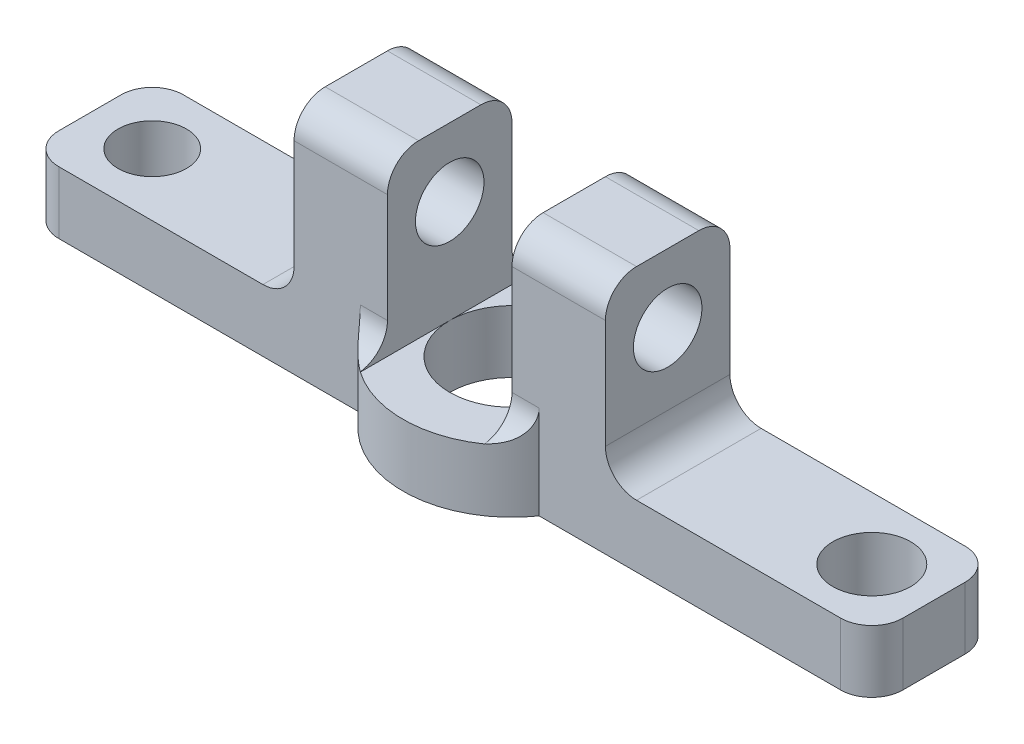
SolidWorks part; units mm, degrees
ref_plane "前视基准面" through (0, 0, 0) normal (0, 0, 1) x (1, 0, 0)
ref_plane "上视基准面" through (0, 0, 0) normal (0, 1, 0) x (1, 0, 0)
ref_plane "右视基准面" through (0, 0, 0) normal (1, 0, 0) x (0, 0, -1)
other "Configuration Table"
sketch "草图1" plane through (0, 0, 0) normal (0, 1, 0) x (1, 0, 0)
  line L0 (-9.561, 0) -> (15.394, 0) construction
  line L5 (15.394, -2) -> (6.0751, -2)
  line L9 (-7.716, 2) -> (1.6029, 2)
  line L11 (6.0751, 2) -> (15.394, 2) construction
  line L13 (15.394, -2) -> (6.0751, -2) construction
  line L18 (-7.716, 2) -> (-9.716, 2)
  line L19 (-9.716, 2) -> (-9.716, -2)
  line L20 (-9.716, -2) -> (-7.716, -2)
  line L21 (15.394, 2) -> (17.394, 2)
  line L22 (17.394, 2) -> (17.394, -2)
  line L23 (17.394, -2) -> (15.394, -2)
  line L24 (6.0751, 2) -> (15.394, 2)
  line L25 (1.6029, -2) -> (-7.716, -2)
  line L26 (1.6029, -2) -> (-7.716, -2) construction
  circle A2 centre (-7.716, 0) radius 1.1
  circle A3 centre (15.394, 0) radius 1.25
  circle A4 centre (3.839, 0) radius 2
  circle A6 centre (3.839, 0) radius 3.5
extrude "凸台-拉伸1" add sketch "草图1" along normal blind 2 contours A2 L5 L9 | A6 L5 L23 L22 L21 L24 A3 | A6 A4 region at (11.8389, 0, 0) region at (3.839, 0, 3.401) region at (-4.2667, 0, 0)
sketch "草图2" plane through (0, 2, 0) normal (0, 1, 0) x (1, 0, 0)
  line L0 (1.839, 0.1576) -> (5.839, 0.1576)
  line L1 (5.839, 2) -> (5.839, -2)
  line L2 (20.339, 2) -> (-12.661, 2) construction
  line L3 (-12.661, -2) -> (20.339, -2) construction
  line L4 (5.839, -2) -> (8.839, -2)
  line L5 (8.839, -2) -> (8.839, 2)
  line L6 (8.839, 2) -> (5.839, 2)
  line L7 (1.839, 2) -> (1.839, -2)
  line L8 (1.839, -2) -> (-1.161, -2)
  line L9 (-1.161, -2) -> (-1.161, 2)
  line L10 (-1.161, 2) -> (1.839, 2)
  point P3 (3.839, 0.1576)
extrude "凸台-拉伸2" add sketch "草图2" along normal blind 5.5 contours L9 L7 | L5 L1 region at (7.339, 2, 0) region at (0.339, 2, 0)
sketch "草图4" plane through (-1.161, 0, 0) normal (-1, 0, 0) x (0, 0, 1)
  line L0 (0, 7.5) -> (0, 7.3) construction
  line L1 (2, 7.5) -> (-2, 7.5) construction
  line L2 (0, 7.3) -> (0, 6.3) construction
  circle A0 centre (0, 5.3) radius 1.1
extrude "切除-拉伸1" cut sketch "草图4" against normal blind 11
fillet "圆角2" radius 1 4 edges at (0.339, 7.5, 2) (0.339, 7.5, -2) (7.339, 7.5, -2) (7.339, 7.5, 2)
fillet "圆角3" radius 1 2 edges at (-1.161, 2, 0) (8.839, 2, 0)
fillet "圆角4" radius 1 4 edges at (-9.716, 1, 2) (-9.716, 1, -2) (17.394, 1, 2) (17.394, 1, -2)
fillet "圆角5" radius 1 4 edges at (1.4029, 2, -2) (6.2752, 2, -2) (6.2752, 2, 2) (1.4029, 2, 2)
